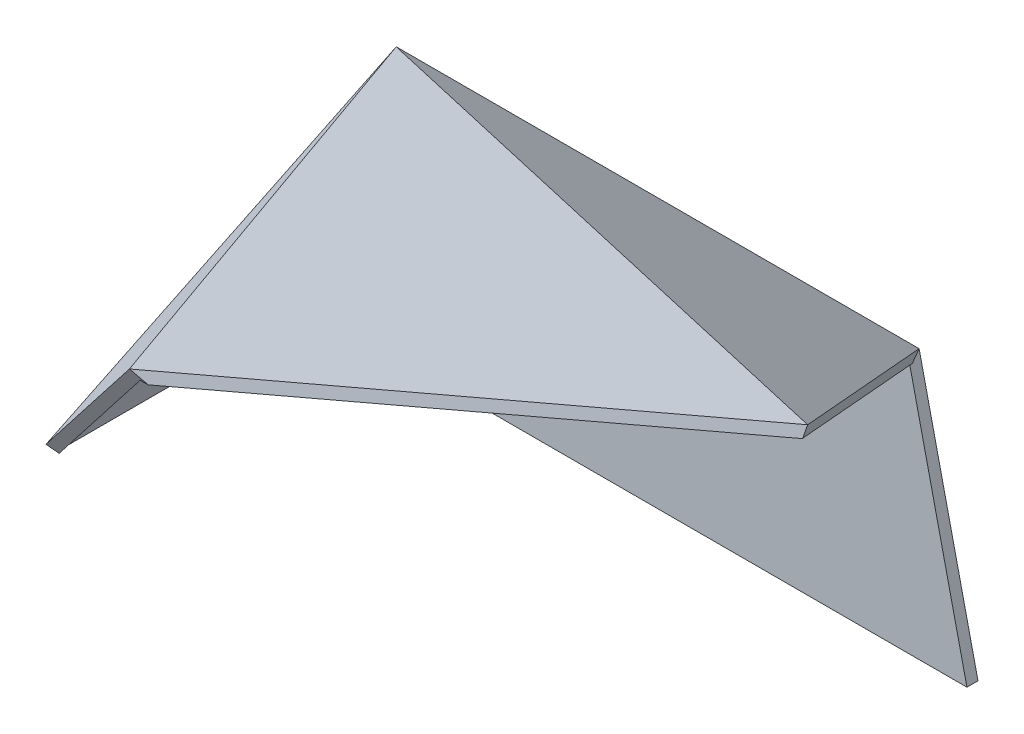
SolidWorks part; units mm, degrees
ref_plane "前视基准面" through (0, 0, 0) normal (0, 0, 1) x (1, 0, 0)
ref_plane "上视基准面" through (0, 0, 0) normal (0, 1, 0) x (1, 0, 0)
ref_plane "右视基准面" through (0, 0, 0) normal (1, 0, 0) x (0, 0, -1)
sketch "Sketch1" plane through (0, 0, 0) normal (0, 0, 1) x (1, 0, 0)
  line L0 (-295, -10) -> (-113.1586, -10)
  line L1 (-295, -10) -> (295, -10) construction
  line L2 (-113.1586, -10) -> (-129.1191, 60)
  line L3 (-129.1191, 60) -> (-270.8573, 60)
  line L4 (-270.8573, 60) -> (-295, -10)
  line L5 (-55, -10) -> (-295, -10) construction
  dimension "D1" = 70
extrude "Extrude1" add sketch "Sketch1" against normal blind 3
sketch "Sketch2" plane through (-260.5569, 89.8651, 0) normal (-0.9454, 0.326, 0) x (0, 0, 1)
  line L0 (0, -31.5915) -> (0, -105.6379)
  line L1 (0, -31.5915) -> (0, -105.6379) construction
  line L2 (0, -105.6379) -> (67.7928, -105.6379)
  line L5 (0, -31.5915) -> (67.7928, -105.6379)
extrude "Extrude2" add sketch "Sketch2" against normal blind 3
ref_plane "Plane1" through (0, 90, 0) normal (0, -1, 0) x (-1, 0, 0)
sketch "Sketch3" plane through (0, 90, 0) normal (0, -1, 0) x (-1, 0, 0)
  line L0 (201.3797, -153.6318) -> (201.3797, -124.7992) construction
  line L2 (226.9384, -143.7928) -> (224.0406, -143.7928) construction
  point P4 (201.3797, -138.7928)
  dimension "D1" = 5
ref_plane "Plane4" through (0, 120, 0) normal (0, 1, 0) x (1, 0, 0)
sketch "Sketch6" plane through (0, 120, 0) normal (0, 1, 0) x (1, 0, 0)
  point P0 (-66.3616, -89.9707)
ref_plane "Plane5" through (0, 43.7249, -28.2185) normal (0, 0.8402, -0.5422) x (1, 0, 0)
sketch "Sketch7" plane through (0, 43.7249, -28.2185) normal (0, 0.8402, -0.5422) x (1, 0, 0)
  line L0 (-66.3616, -140.6648) -> (-129.1191, -30.0142)
  line L1 (-129.1191, -30.0142) -> (-270.8573, -30.0142)
  line L2 (-270.8573, -30.0142) -> (-66.3616, -140.6648)
extrude "Extrude4" add sketch "Sketch7" against normal blind 3
ref_axis "Axis1" through (-270.8573, 60, -3) along (-0.2357, -0.6833, 0.691)
ref_plane "Plane6" through (-194.9332, 134.9532, 66.9631) normal (-0.7912, 0.5478, 0.2718) x (0.225, -0.1525, 0.9623)
sketch "Sketch8" plane through (-194.9332, 134.9532, 66.9631) normal (-0.7912, 0.5478, 0.2718) x (0.225, -0.1525, 0.9623)
  line L0 (74.5289, -40.8326) -> (-72.9852, -104.6444)
  line L1 (-72.9852, -104.6444) -> (0.3827, -176.1401)
  line L2 (0.3827, -176.1401) -> (74.5289, -40.8326)
extrude "Extrude5" add sketch "Sketch8" against normal blind 3
ref_plane "Plane7" through (-30.5316, 120.3261, -10.4979) normal (-0.2451, 0.9658, -0.0843) x (0.9695, 0.2441, -0.0213)
sketch "Sketch9" plane through (-30.5316, 120.3261, -10.4979) normal (-0.2451, 0.9658, -0.0843) x (0.9695, 0.2441, -0.0213)
  line L0 (-36.9571, -100.06) -> (-176.222, -146.0899)
  line L1 (-176.222, -146.0899) -> (-247.8849, -2.2263)
  line L2 (-247.8849, -2.2263) -> (-36.9571, -100.06)
extrude "Extrude6" add sketch "Sketch9" against normal blind 3
sketch "Sketch10" plane through (-194.9332, 134.9532, 66.9631) normal (-0.7912, 0.5478, 0.2718) x (0.2235, -0.1547, 0.9624)
  line L1 (-95.6876, -88.5386) -> (16.8839, -88.5386)
  line L2 (-95.6876, -88.5386) -> (-95.6876, -178.6946)
  line L3 (-95.6876, -178.6946) -> (16.8839, -178.6946)
  line L4 (16.8839, -88.5386) -> (16.8839, -178.6946)
extrude "Extrude7" cut sketch "Sketch10" along normal blind 3
sketch "Sketch11" plane through (0, 0, -3) normal (0, 0, -1) x (-1, 0, 0)
  line L1 (239.3397, 70.1877) -> (313.0975, 70.1877)
  line L2 (239.3397, 70.1877) -> (239.3397, 55.4282)
  line L3 (239.3397, 55.4282) -> (313.0975, 55.4282)
  line L4 (313.0975, 70.1877) -> (313.0975, 55.4282)
extrude "Extrude8" cut sketch "Sketch11" along normal blind 3
sketch "Sketch12" plane through (0, -10, 0) normal (0, -1, 0) x (1, 0, 0)
  line L1 (-355.8844, -24.4832) -> (-188.0129, -24.4832)
  line L2 (-355.8844, -24.4832) -> (-355.8844, 171.382)
  line L3 (-355.8844, 171.382) -> (-188.0129, 171.382)
  line L4 (-188.0129, -24.4832) -> (-188.0129, 171.382)
extrude "Extrude10" cut sketch "Sketch12" along normal blind 3
sketch "Sketch13" plane through (-6.4507, -44.9577, 71.8265) normal (-0.0759, -0.529, 0.8452) x (0.9971, -0.0403, 0.0643)
  line L1 (-217.8128, 155.7733) -> (-173.2445, 155.7733)
  line L2 (-217.8128, 155.7733) -> (-217.8128, 131.2611)
  line L3 (-217.8128, 131.2611) -> (-173.2445, 131.2611)
  line L4 (-173.2445, 155.7733) -> (-173.2445, 131.2611)
extrude "Extrude11" cut sketch "Sketch13" along normal blind 3
sketch "Sketch14" plane through (25.3769, 13.2736, 78.3364) normal (0.3043, 0.1591, 0.9392) x (0.9526, -0.0508, -0.3)
  line L1 (-122.9735, 108.9795) -> (-62.7635, 108.9795)
  line L2 (-122.9735, 108.9795) -> (-122.9735, 92.9613)
  line L3 (-122.9735, 92.9613) -> (-62.7635, 92.9613)
  line L4 (-62.7635, 108.9795) -> (-62.7635, 92.9613)
extrude "Extrude12" cut sketch "Sketch14" along normal blind 3
sketch "Sketch15" plane through (-110.5731, 34.0063, 52.6931) normal (0.8698, -0.2675, -0.4145) x (-0.3962, 0.1219, -0.91)
  line L1 (-45.3554, 87.1221) -> (-30.4661, 87.1221)
  line L2 (-45.3554, 87.1221) -> (-45.3554, 100.6095)
  line L3 (-45.3554, 100.6095) -> (-30.4661, 100.6095)
  line L4 (-30.4661, 87.1221) -> (-30.4661, 100.6095)
extrude "Extrude13" cut sketch "Sketch15" along normal blind 3
